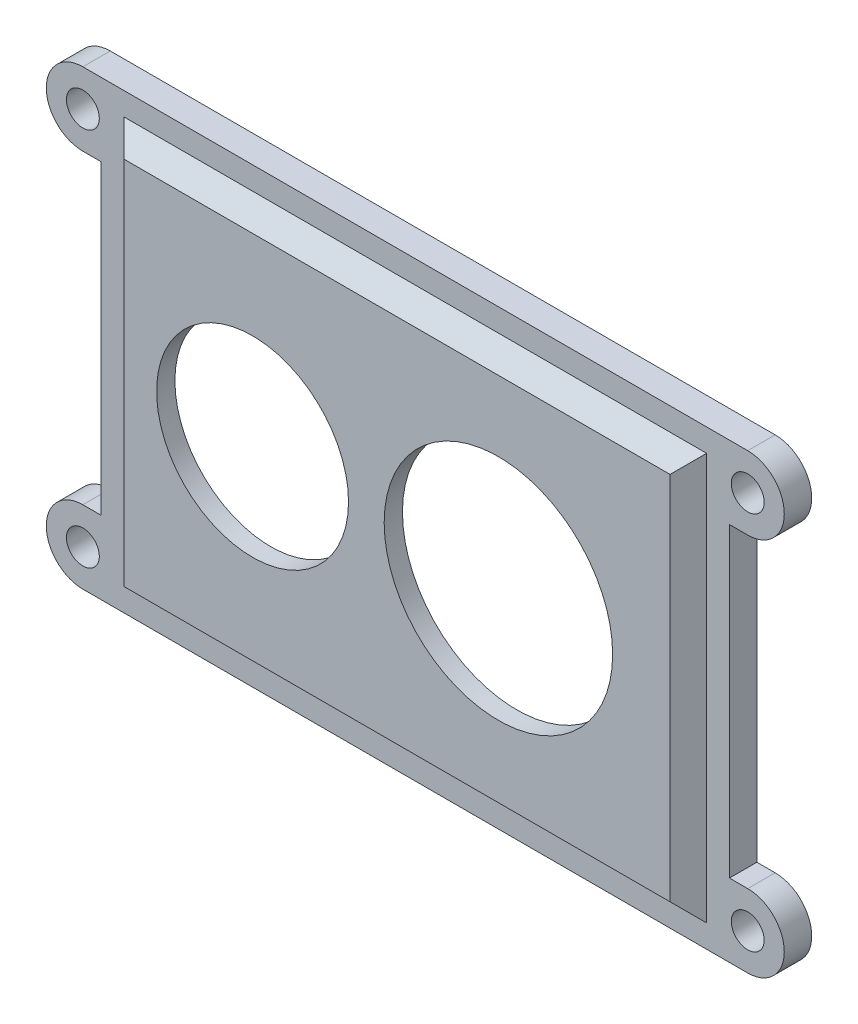
SolidWorks part; units mm, degrees
ref_plane "Plano frontal" through (0, 0, 0) normal (0, 0, 1) x (1, 0, 0)
ref_plane "Plano superior" through (0, 0, 0) normal (0, 1, 0) x (1, 0, 0)
ref_plane "Plano direito" through (0, 0, 0) normal (1, 0, 0) x (0, 0, -1)
sketch "Esboço1" plane through (0, 0, 0) normal (0, 0, 1) x (1, 0, 0)
  line L1 (34.375, -24.75) -> (-34.375, -24.75)
  line L2 (34.375, -24.75) -> (34.375, 24.75)
  line L3 (34.375, 24.75) -> (-34.375, 24.75)
  line L4 (-34.375, -24.75) -> (-34.375, 24.75)
  line L5 (34.375, -24.75) -> (-34.375, 24.75) construction
  line L6 (34.375, 24.75) -> (-34.375, -24.75) construction
  point P0 (0, 0)
  dimension "D1" = 68.75
  dimension "D2" = 49.5
extrude "Ressalto-extrusão1" add sketch "Esboço1" along normal blind 5
sketch "Esboço2" plane through (0, 0, 0) normal (0, 0, -1) x (-1, 0, 0)
  line L1 (30.375, -20.5) -> (-30.375, -20.5)
  line L2 (30.375, -20.5) -> (30.375, 20.5)
  line L3 (30.375, 20.5) -> (-30.375, 20.5)
  line L4 (-30.375, -20.5) -> (-30.375, 20.5)
  line L5 (30.375, -20.5) -> (-30.375, 20.5) construction
  line L6 (30.375, 20.5) -> (-30.375, -20.5) construction
  point P0 (0, 0)
  dimension "D1" = 60.75
  dimension "D2" = 41
extrude "Corte-extrusão1" cut sketch "Esboço2" against normal blind 3
sketch "Esboço3" plane through (0, 0, 0) normal (0, 0, -1) x (-1, 0, 0)
  line L0 (-36.375, 24.75) -> (-34.375, 24.75)
  line L1 (-34.375, 24.75) -> (-34.375, 16.75)
  line L2 (-34.375, 16.75) -> (-36.375, 16.75)
  line L3 (0, 2.75) -> (0, -2.75) construction
  line L4 (34.375, 16.75) -> (36.375, 16.75)
  line L5 (34.375, 24.75) -> (34.375, 16.75)
  line L6 (36.375, 24.75) -> (34.375, 24.75)
  line L7 (2.75, 0) -> (-2.75, 0) construction
  line L8 (36.375, -24.75) -> (34.375, -24.75)
  line L9 (34.375, -24.75) -> (34.375, -16.75)
  line L10 (34.375, -16.75) -> (36.375, -16.75)
  line L11 (-34.375, -16.75) -> (-36.375, -16.75)
  line L12 (-34.375, -24.75) -> (-34.375, -16.75)
  line L13 (-36.375, -24.75) -> (-34.375, -24.75)
  line L14 (-34.375, -24.75) -> (-34.375, 24.75) construction
  arc A8 (-36.375, 24.75) -> (-36.375, 16.75) centre (-36.375, 20.75) ccw
  circle A9 centre (-36.375, 20.75) radius 1.8
  circle A11 centre (36.375, 20.75) radius 1.8
  arc A12 (36.375, 24.75) -> (36.375, 16.75) centre (36.375, 20.75) cw
  arc A13 (36.375, -24.75) -> (36.375, -16.75) centre (36.375, -20.75) ccw
  circle A14 centre (36.375, -20.75) radius 1.8
  circle A15 centre (-36.375, -20.75) radius 1.8
  arc A16 (-36.375, -24.75) -> (-36.375, -16.75) centre (-36.375, -20.75) cw
  point P3 (0, 0)
  point P4 (0, 0)
  point P34 (0, 0)
  point P35 (-34.375, 16.7508)
  point P38 (0, 0)
  point P39 (-34.375, 17.8085)
  point P40 (0, 0)
  point P41 (-34.375, 20.75)
  point P42 (0, 0)
  point P43 (0, 0)
  dimension "D1" = 8
  dimension "D2" = 3.6
  dimension "D3" = 2
extrude "Ressalto-extrusão2" add sketch "Esboço3" against normal blind 3
sketch "Esboço4" plane through (0, 0, 5) normal (0, 0, 1) x (1, 0, 0)
  line L5 (34.375, -24.75) -> (-34.375, -24.75)
  line L6 (34.375, -24.75) -> (34.375, 24.75)
  line L8 (34.375, 24.75) -> (-34.375, 24.75)
  line L13 (-34.375, -24.75) -> (-34.375, 24.75)
  line L14 (34.375, -24.75) -> (-34.375, 24.75) construction
  line L15 (34.375, 24.75) -> (-34.375, -24.75) construction
  line L16 (31.875, -22.25) -> (-31.875, -22.25)
  line L17 (31.875, -22.25) -> (31.875, 22.25)
  line L18 (31.875, 22.25) -> (-31.875, 22.25)
  line L19 (-31.875, -22.25) -> (-31.875, 22.25)
  line L20 (31.875, -22.25) -> (-31.875, 22.25) construction
  line L21 (31.875, 22.25) -> (-31.875, -22.25) construction
  point P0 (0, 0)
  point P6 (0, 0)
  line M6 (-34.375, 24.75) -> (-34.375, -24.75)
  line M7 (-34.375, -24.75) -> (34.375, -24.75)
  line M8 (34.375, -24.75) -> (34.375, 24.75)
  line M9 (34.375, 24.75) -> (-34.375, 24.75)
  dimension "D1" = 2.5
  dimension "D2" = 2.5
extrude "Corte-extrusão2" cut sketch "Esboço4" against normal up to surface (2 mm away) contours L16 L19 L18 L17 M9 M6 M7 M8 region at (0, -23.9028, 5) up to face at (-34.575, 20.75, 3)
sketch "Esboço5" plane through (0, 0, 0) normal (0, 0, -1) x (-1, 0, 0)
chamfer "Chanfro1" distance 2 angle 45 4 edges at (31.875, 0, 5) (0, -22.25, 5) (-31.875, 0, 5) (0, 22.25, 5)
sketch "Esboço6" plane through (0, 0, 5) normal (0, 0, 1) x (1, 0, 0)
  line L0 (-29.875, -20.25) -> (29.875, -20.25) construction
  line L1 (-29.875, 20.25) -> (-29.875, -20.25) construction
  line L2 (29.875, -20.25) -> (29.875, 20.25) construction
  circle A0 centre (11.0945, 0.05) radius 11.5 construction
  circle A1 centre (-15.8055, 0.05) radius 9.5 construction
  circle A2 centre (-15.8055, 0.05) radius 10.5
  circle A3 centre (11.0945, 0.05) radius 12.5
  point P18 (46.9211, -7.0458)
  dimension "D1" = 1
  dimension "D2" = 1
  dimension "D3" = 19
  dimension "D4" = 20.3
  dimension "D6" = 23
  dimension "D5" = 14.0695
  dimension "D7" = 20.3
  dimension "D8" = 18.7805
extrude "Corte-extrusão4" cut sketch "Esboço6" against normal through all
